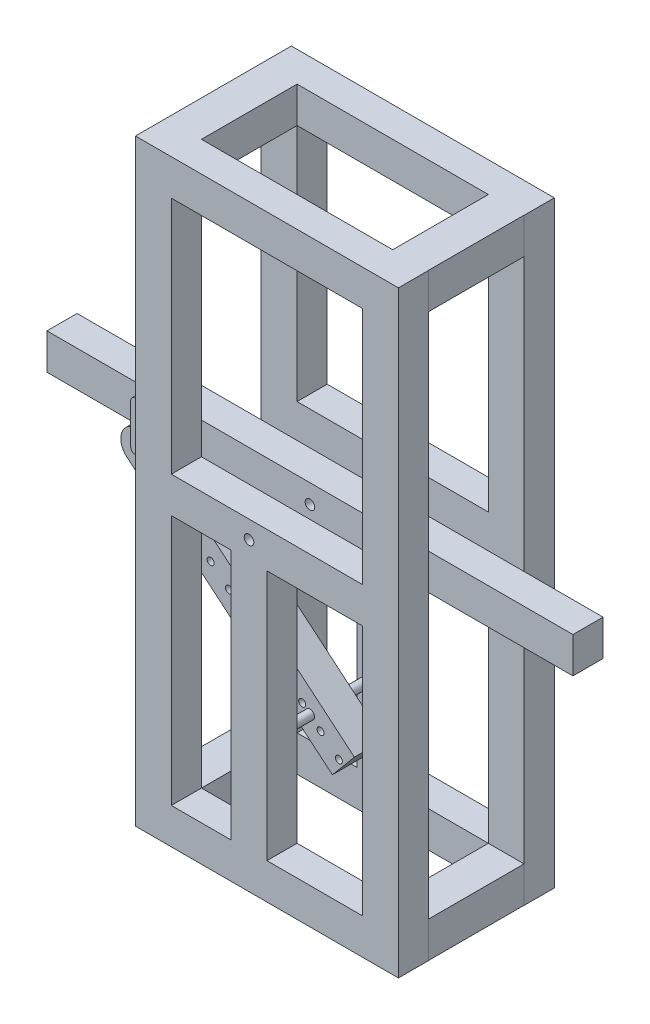
SolidWorks part; units mm, degrees
note: The reader was unsure of these and kept them because the rebuilt part matched: shared geometry of "Esquisse11<3>".
ref_plane "Plan de face" through (0, 0, 0) normal (0, 0, 1) x (1, 0, 0)
ref_plane "Plan de dessus" through (0, 0, 0) normal (0, 1, 0) x (1, 0, 0)
ref_plane "Plan de droite" through (0, 0, 0) normal (1, 0, 0) x (0, 0, -1)
sketch "Esquisse1" plane through (0, 0, 0) normal (0, 0, 1) x (1, 0, 0)
  line L0 (0, 0) -> (0, 1250)
  line L1 (0, 1250) -> (550, 1250)
  line L2 (550, 1250) -> (550, 0)
  line L3 (550, 0) -> (0, 0)
  line L4 (75, 75) -> (200, 75)
  line L5 (200, 75) -> (200, 600)
  line L6 (200, 600) -> (75, 600)
  line L7 (75, 600) -> (75, 75)
  line L8 (275, 75) -> (275, 600)
  line L9 (275, 75) -> (475, 75)
  line L10 (275, 600) -> (475, 600)
  line L11 (475, 75) -> (475, 600)
  line L12 (75, 1175) -> (475, 1175)
  line L13 (75, 1175) -> (75, 675)
  line L14 (475, 1175) -> (475, 675)
  line L15 (75, 675) -> (475, 675)
  line L16 (0, 576.4266) -> (550, 576.4266) construction
  line L17 (275, 0) -> (275, 675) construction
  dimension "D1" = 75
  dimension "D2" = 75
  dimension "D3" = 75
  dimension "D4" = 550
  dimension "D5" = 1250
  dimension "D6" = 75
  dimension "D7" = 75
  dimension "D8" = 500
  dimension "D9" = 75
  dimension "D10" = 75
  dimension "D11" = 75
  dimension "D12" = 75
  dimension "D13" = 200
extrude "Boss.-Extru.1" add sketch "Esquisse1" along normal blind 63
pattern_linear "Répétition linéaire1" count 2 spacing 263 along (0, 0, 1) of "Boss.-Extru.1"
sketch "Esquisse2" plane through (0, 0, 63) normal (0, 0, 1) x (1, 0, 0)
  line L0 (75, 75) -> (75, 0)
  line L1 (75, 75) -> (0, 75)
  line L2 (75, 0) -> (0, 0)
  line L3 (0, 75) -> (0, 0)
  line L4 (0, 0) -> (550, 0) construction
  line L6 (475, 75) -> (475, 0)
  line L7 (475, 75) -> (549.7182, 75)
  line L8 (475, 0) -> (549.7182, 0)
  line L9 (549.7182, 75) -> (549.7182, 0)
  line L10 (475, 1175) -> (475, 1250)
  line L11 (475, 1175) -> (549.7182, 1175)
  line L12 (475, 1250) -> (549.7182, 1250)
  line L13 (549.7182, 1175) -> (549.7182, 1250)
  line L14 (550, 1250) -> (0, 1250) construction
  line L15 (75, 1175) -> (75, 1250)
  line L16 (75, 1175) -> (0, 1175)
  line L17 (75, 1250) -> (0, 1250)
  line L18 (0, 1175) -> (0, 1250)
extrude "Boss.-Extru.2" add sketch "Esquisse2" along normal blind 200
ref_plane "Plan5" through (237.5, 0, 0) normal (-1, 0, 0) x (0, 0, 1)
sketch "Esquisse7" plane through (237.5, 0, 0) normal (-1, 0, 0) x (0, 0, 1)
  line L0 (135.5851, 602.1492) -> (198.5851, 602.1492)
  line L1 (135.5851, 602.1492) -> (135.5851, 677.1492)
  line L2 (198.5851, 602.1492) -> (198.5851, 677.1492)
  line L3 (135.5851, 677.1492) -> (198.5851, 677.1492)
  line L5 (135.5851, 677.1492) -> (198.5851, 602.1492) construction
  line L6 (198.5851, 677.1492) -> (135.5851, 602.1492) construction
  dimension "D1" = 63
  dimension "D2" = 75
sketch "Esquisse8" plane through (475, 0, 0) normal (-1, 0, 0) x (0, 0, 1)
  line L0 (263, 600) -> (63, 675) construction
  line L1 (63, 600) -> (263, 675) construction
extrude "Boss.-Extru.4" add sketch "Esquisse7" along normal blind 550 and the other way blind 550 separate body
sketch "Esquisse3" plane through (0, 0, 326) normal (0, 0, 1) x (1, 0, 0)
  line L0 (75, 675) -> (75, 600) construction
  line L1 (75, 675) -> (475, 675) construction
  line L2 (75, 637.5) -> (476.0322, 637.5) construction
  line L3 (200, 600) -> (275, 675) construction
  circle A0 centre (237.5, 637.5) radius 10
extrude "Enlèv. mat.-Extru.2" cut sketch "Esquisse3" against normal through all
sketch "Esquisse11" plane through (0, 0, 198.5851) normal (0, 0, 1) x (1, 0, 0)
  line L1 (-99.1531, 586.9143) -> (330.5036, 226.557)
  line L2 (-145.2214, 531.9867) -> (284.4353, 171.6294)
  line L3 (330.5036, 226.557) -> (284.4353, 171.6294)
  line L4 (-122.1872, 559.4505) -> (-122.1872, 643.6137) construction
  line L5 (-114.55, 559.4505) -> (-114.55, 643.6137)
  line L7 (-132.34, 643.6137) -> (-132.34, 559.4505)
  arc A0 (-99.1531, 586.9143) -> (-145.2214, 531.9867) centre (-122.1872, 559.4505) ccw
  arc A1 (-132.34, 559.4505) -> (-114.55, 559.4505) centre (-123.445, 559.4505) ccw
  arc A2 (-114.55, 643.6137) -> (-132.34, 643.6137) centre (-123.445, 643.6137) ccw
extrude "Boss.-Extru.5" add sketch "Esquisse11" against normal blind 63 separate body
extrude "Boss.-Extru.6" add sketch "Esquisse11<3>" along normal blind 5
sketch "Esquisse11<3>" plane through (0, 0, 198.5851) normal (0, 0, 1) x (1, 0, 0) same geometry as "Esquisse11"
sketch "Esquisse12" plane through (0, 0, 198.5851) normal (0, 0, 1) x (1, 0, 0)
  line L2 (307.4695, 199.0932) -> (-123.445, 559.4505) construction
  line L3 (330.5036, 226.557) -> (284.4353, 171.6294) construction
  circle A0 centre (-123.445, 559.4505) radius 7.3554
extrude "Enlèv. mat.-Extru.3" cut sketch "Esquisse12" against normal blind 100
pattern_linear "Répétition linéaire2" count 12 spacing 50 along (0.7662, -0.6426, 0) of "Enlèv. mat.-Extru.3"
sketch "Esquisse13" plane through (0, 0, 326) normal (0, 0, 1) x (1, 0, 0)
  line L0 (237.5, 144.65) -> (237.5, -144.65) construction
  circle A0 centre (237.5, 257.6084) radius 9.504
extrude "Boss.-Extru.7" add sketch "Esquisse13" against normal through all
